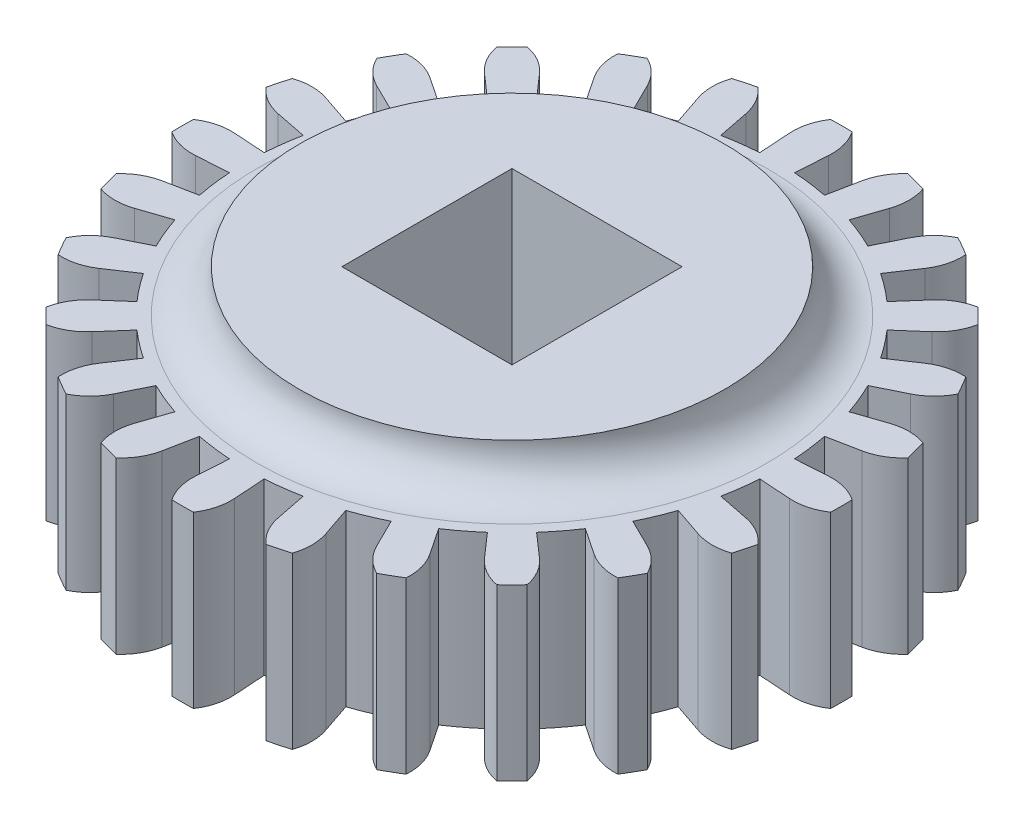
SolidWorks part; units mm, degrees
ref_plane "Front Plane" through (0, 0, 0) normal (0, 0, 1) x (1, 0, 0)
ref_plane "Top Plane" through (0, 0, 0) normal (0, 1, 0) x (1, 0, 0)
ref_plane "Right Plane" through (0, 0, 0) normal (1, 0, 0) x (0, 0, -1)
sketch "Sketch10" plane through (0, 0, 0) normal (0, 1, 0) x (1, 0, 0)
  line L0 (0, 0) -> (28.3448, 0) construction
  line L1 (0, 0) -> (12.3931, 1.6316) construction
  line L2 (0, 0) -> (21.5394, 1.4118) construction
  line L3 (0, 0) -> (24.4578, 0.8007) construction
  line L4 (13.97, 0.9156) -> (12.4732, 0.8175)
  line L5 (0, 0) -> (12.3931, 1.6316)
  line L9 (0, 0) -> (12.3931, -1.6316)
  line L13 (12.4732, -0.8175) -> (13.97, -0.9156)
  circle A0 centre (0, 0) radius 12.5 construction
  circle A1 centre (0, 0) radius 14 construction
  circle A2 centre (0, 0) radius 15.5 construction
  arc A3 (13.97, 0.9156) -> (15.4917, 0.5071) centre (14.1301, -1.5265) cw
  arc A4 (12.3931, 1.6316) -> (12.4732, 0.8175) centre (0, 0) cw
  arc A5 (13.97, -0.9156) -> (15.4917, -0.5071) centre (14.1301, 1.5265) ccw
  arc A6 (12.3931, -1.6316) -> (12.4732, -0.8175) centre (0, 0) ccw
  arc A7 (15.4917, 0.5071) -> (15.4917, -0.5071) centre (0, 0) cw
  dimension "D1" = 25
  dimension "D2" = 28
  dimension "D3" = 31
  dimension "D4" = 7.5
  dimension "D5" = 3.75
  dimension "D6" = 1.875
  dimension "D7" = 0
  dimension "D8" = 0
extrude "Boss-Extrude3" add sketch "Sketch10" along normal blind 8 contours A7 A3 L4 A4 L5 L9 A6 L13 A5 region at (9.4175, 0, 0)
pattern_circular "CirPattern1" count 24 every 15 about axis through (0, 8, 0) along (0, -1, 0) of "Boss-Extrude3" reverse direction yes
sketch "Sketch12" plane through (0, 0, 0) normal (0, -1, 0) x (1, 0, 0)
  line L1 (4, 4) -> (-4, 4)
  line L2 (4, 4) -> (4, -4)
  line L3 (4, -4) -> (-4, -4)
  line L4 (-4, 4) -> (-4, -4)
  arc A0 (12.2598, -2.4386) -> (12.4732, -0.8175) centre (0, 0) ccw construction
  arc A1 (-5.5286, -11.2109) -> (-4.018, -11.8366) centre (0, 0) ccw construction
  dimension "D1" = 4
  dimension "D2" = 8
  dimension "D3" = 4
  dimension "D4" = 8
extrude "Cut-Extrude1" cut sketch "Sketch12" against normal through all
sketch "Sketch13" plane through (0, 8, 0) normal (0, 1, 0) x (1, 0, 0)
  line L1 (4, 4) -> (-4, 4)
  line L2 (4, 4) -> (4, -4)
  line L3 (4, -4) -> (-4, -4)
  line L4 (-4, 4) -> (-4, -4)
  circle A0 centre (0, 0) radius 10
  dimension "D1" = 20
extrude "Boss-Extrude4" add sketch "Sketch13" along normal blind 2
fillet "Fillet1" radius 2 1 edges at (0, 8, 10)
